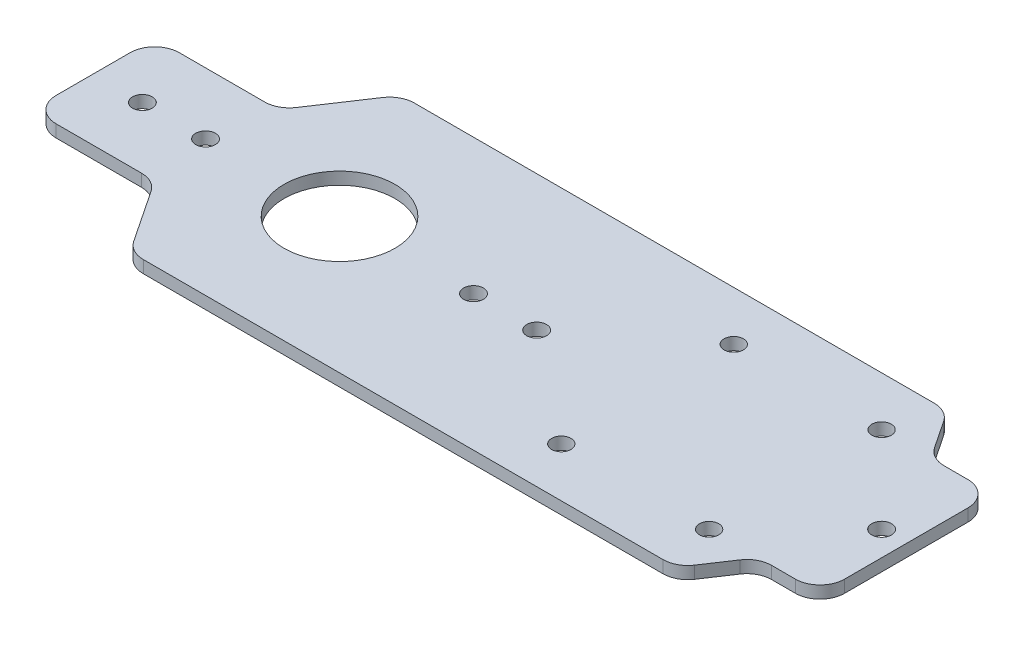
SolidWorks part; units mm, degrees
material "6061 Alloy"
ref_plane "Front Plane" through (0, 0, 0) normal (0, 0, 1) x (1, 0, 0)
ref_plane "Top Plane" through (0, 0, 0) normal (0, 1, 0) x (1, 0, 0)
ref_plane "Right Plane" through (0, 0, 0) normal (1, 0, 0) x (0, 0, -1)
sketch "Sketch1" plane through (0, 0, 0) normal (0, 1, 0) x (1, 0, 0)
  line L0 (16.2686, 0) -> (85.3314, 0) construction
  line L1 (50.8, 0) -> (50.8, 3.1391) construction
  line L2 (19.05, 15.875) -> (31.75, 34.925)
  line L3 (-12.7, 15.875) -> (19.05, 15.875)
  line L4 (-12.7, 15.875) -> (-12.7, -15.875)
  line L5 (-12.7, -15.875) -> (19.05, -15.875)
  line L6 (114.3, 15.875) -> (114.3, -15.875)
  line L7 (-12.7, 15.875) -> (114.3, -15.875) construction
  line L8 (-12.7, -15.875) -> (114.3, 15.875) construction
  line L9 (31.75, 34.925) -> (69.85, 34.925)
  line L10 (69.85, 34.925) -> (82.55, 15.875)
  line L11 (50.8, 34.925) -> (50.8, 29.0511) construction
  line L12 (69.85, -34.925) -> (82.55, -15.875)
  line L13 (31.75, -34.925) -> (69.85, -34.925)
  line L14 (19.05, -15.875) -> (31.75, -34.925)
  line L15 (82.55, -15.875) -> (114.3, -15.875)
  line L16 (82.55, 15.875) -> (114.3, 15.875)
  circle A0 centre (0, 0) radius 2.54
  circle A1 centre (101.6, 0) radius 2.54
  circle A2 centre (16.2686, 0) radius 2.54 construction
  circle A3 centre (85.3314, 0) radius 2.54 construction
  dimension "D1" = 5.08
  dimension "D3" = 127
  dimension "D4" = 31.75
  dimension "D5" = 69.0628
  dimension "D2" = 101.6
  dimension "D6" = 19.05
  dimension "D7" = 31.75
  dimension "D8" = 38.1
extrude "Boss-Extrude1" add sketch "Sketch1" along normal blind 3.175
sketch "Sketch2" plane through (0, 3.175, 0) normal (0, 1, 0) x (1, 0, 0)
  circle A0 centre (50.8, 0) radius 14.2875
  circle A1 centre (0, 0) radius 2.54 construction
  dimension "D1" = 50.8
  dimension "D2" = 28.575
extrude "Cut-Extrude1" cut sketch "Sketch2" against normal blind 3.175
sketch "Sketch3" plane through (0, 3.175, 0) normal (0, 1, 0) x (1, 0, 0)
  line L0 (50.8, 0) -> (50.8, 14.2875) construction
  circle A2 centre (85.3314, 0) radius 2.54
  circle A3 centre (16.2686, 0) radius 2.54
  circle A5 centre (50.8, 0) radius 14.2875 construction
  circle A6 centre (50.8, 0) radius 14.2875 construction
  dimension "D2" = 5.08
  dimension "D3" = 5.08
  dimension "D4" = 69.0628
extrude "Cut-Extrude2" cut sketch "Sketch3" against normal through all
sketch "Sketch5" plane through (0, 0, 0) normal (0, -1, 0) x (1, 0, 0)
  line L5 (114.3, 15.875) -> (114.3, -15.875) construction
  line L10 (69.85, -34.925) -> (196.85, -34.925)
  line L11 (69.85, -34.925) -> (69.85, 34.925)
  line L12 (69.85, 34.925) -> (196.85, 34.925)
  line L13 (196.85, -34.925) -> (196.85, 34.925)
  line L14 (114.554, 17.272) -> (183.896, 17.272) construction
  line L15 (114.554, 17.272) -> (114.554, -17.272) construction
  line L16 (114.554, -17.272) -> (183.896, -17.272) construction
  line L17 (183.896, 17.272) -> (183.896, -17.272) construction
  line L18 (172.5083, 34.925) -> (180.975, 22.225)
  line L19 (172.5083, -34.925) -> (180.975, -22.225)
  line L20 (180.975, -22.225) -> (196.85, -22.225)
  line L21 (82.55, -15.875) -> (69.85, -34.925) construction
  line L22 (82.55, -15.875) -> (69.85, -34.925)
  line L23 (69.85, 34.925) -> (82.55, 15.875) construction
  line L24 (69.85, 34.925) -> (82.55, 15.875)
  line L25 (180.975, 22.225) -> (196.85, 22.225)
  circle A4 centre (101.6, 0) radius 2.54 construction
  circle A5 centre (85.3314, 0) radius 2.54 construction
  circle A6 centre (101.6, 0) radius 2.54
  circle A7 centre (85.3314, 0) radius 2.54
  circle A8 centre (130.175, 22.225) radius 2.4892
  circle A9 centre (168.275, 22.225) radius 2.4892
  circle A10 centre (130.175, -22.225) radius 2.4892
  circle A11 centre (168.275, -22.225) radius 2.4892
  circle A12 centre (190.5, 0) radius 2.54
  line M15 (69.85, -34.925) -> (82.55, -15.875)
  line M16 (82.55, -15.875) -> (114.3, -15.875)
  line M17 (114.3, -15.875) -> (114.3, 15.875)
  line M18 (114.3, 15.875) -> (82.55, 15.875)
  line M19 (82.55, 15.875) -> (69.85, 34.925)
  dimension "D2" = 4.9784
  dimension "D3" = 44.45
  dimension "D4" = 38.1
  dimension "D11" = 15.621
  dimension "D16" = 88.9
  dimension "D5" = 4.953
  dimension "D6" = 82.55
  dimension "D7" = 17.653
  dimension "D8" = 0.254
  dimension "D9" = 69.342
  dimension "D10" = 34.544
  dimension "D12" = 15.875
  dimension "D13" = 12.7
  dimension "D14" = 15.875
  dimension "D15" = 12.7
extrude "Boss-Extrude2" add sketch "Sketch5" against normal up to surface (3.175 mm away) contours L25 L18 L12 L10 L19 L20 L13 A11 A10 A9 A8 M19 M18 M17 M16 M15 region at (139.8524, 0, 0) up to face at (85.3314, 3.175, 2.54)
fillet "Fillet1" radius 6.35 12 edges at (19.05, 1.5875, -15.875) (31.75, 1.5875, -34.925) (31.75, 1.5875, 34.925) (19.05, 1.5875, 15.875) (-12.7, 1.5875, -15.875) (-12.7, 1.5875, 15.875) (172.5083, 1.5875, -34.925) (180.975, 1.5875, -22.225) (196.85, 1.5875, -22.225) (196.85, 1.5875, 22.225) (180.975, 1.5875, 22.225) (172.5083, 1.5875, 34.925)
sketch "Sketch4"
sketch "Sketch6" plane through (0, 3.175, 0) normal (0, 1, 0) x (1, 0, 0)
  line L12 (179.0899, 25.0527) -> (174.3934, 32.0973)
  line L13 (169.1099, 34.925) -> (35.1484, 34.925)
  line L14 (29.8649, 32.0973) -> (20.9351, 18.7027)
  line L15 (15.6516, 15.875) -> (-6.35, 15.875)
  line L16 (-12.7, 9.525) -> (-12.7, -9.525)
  line L17 (-6.35, -15.875) -> (15.6516, -15.875)
  line L18 (20.9351, -18.7027) -> (29.8649, -32.0973)
  line L19 (35.1484, -34.925) -> (169.1099, -34.925)
  line L20 (174.3934, -32.0973) -> (179.0899, -25.0527)
  line L21 (184.3734, -22.225) -> (190.5, -22.225)
  line L22 (196.85, -15.875) -> (196.85, 15.875)
  line L23 (190.5, 22.225) -> (184.3734, 22.225)
  line L24 (179.0899, 25.0527) -> (174.3934, 32.0973)
  line L25 (169.1099, 34.925) -> (35.1484, 34.925)
  line L26 (29.8649, 32.0973) -> (20.9351, 18.7027)
  line L27 (15.6516, 15.875) -> (-6.35, 15.875)
  line L28 (-12.7, 9.525) -> (-12.7, -9.525)
  line L29 (-6.35, -15.875) -> (15.6516, -15.875)
  line L30 (20.9351, -18.7027) -> (29.8649, -32.0973)
  line L31 (35.1484, -34.925) -> (169.1099, -34.925)
  line L32 (174.3934, -32.0973) -> (179.0899, -25.0527)
  line L33 (184.3734, -22.225) -> (190.5, -22.225)
  line L34 (196.85, -15.875) -> (196.85, 15.875)
  line L35 (190.5, 22.225) -> (184.3734, 22.225)
  circle A0 centre (0, 0) radius 2.54 construction
  circle A1 centre (16.2686, 0) radius 2.54 construction
  circle A2 centre (50.8, 0) radius 14.2875 construction
  circle A3 centre (85.3314, 0) radius 2.54 construction
  circle A4 centre (130.175, -22.225) radius 2.4892 construction
  circle A5 centre (101.6, 0) radius 2.54 construction
  circle A6 centre (130.175, 22.225) radius 2.4892 construction
  circle A7 centre (168.275, 22.225) radius 2.4892 construction
  circle A8 centre (190.5, 0) radius 2.54 construction
  circle A9 centre (168.275, -22.225) radius 2.4892 construction
  circle A10 centre (0, 0) radius 2.54
  circle A11 centre (16.2686, 0) radius 2.54
  arc A12 (174.3934, 32.0973) -> (169.1099, 34.925) centre (169.1099, 28.575) ccw
  arc A13 (35.1484, 34.925) -> (29.8649, 32.0973) centre (35.1484, 28.575) ccw
  arc A14 (15.6516, 15.875) -> (20.9351, 18.7027) centre (15.6516, 22.225) ccw
  arc A15 (-6.35, 15.875) -> (-12.7, 9.525) centre (-6.35, 9.525) ccw
  arc A16 (-12.7, -9.525) -> (-6.35, -15.875) centre (-6.35, -9.525) ccw
  arc A17 (20.9351, -18.7027) -> (15.6516, -15.875) centre (15.6516, -22.225) ccw
  arc A18 (29.8649, -32.0973) -> (35.1484, -34.925) centre (35.1484, -28.575) ccw
  arc A19 (169.1099, -34.925) -> (174.3934, -32.0973) centre (169.1099, -28.575) ccw
  arc A20 (184.3734, -22.225) -> (179.0899, -25.0527) centre (184.3734, -28.575) ccw
  arc A21 (190.5, -22.225) -> (196.85, -15.875) centre (190.5, -15.875) ccw
  arc A22 (196.85, 15.875) -> (190.5, 22.225) centre (190.5, 15.875) ccw
  arc A23 (179.0899, 25.0527) -> (184.3734, 22.225) centre (184.3734, 28.575) ccw
  arc A24 (174.3934, 32.0973) -> (169.1099, 34.925) centre (169.1099, 28.575) ccw
  arc A25 (35.1484, 34.925) -> (29.8649, 32.0973) centre (35.1484, 28.575) ccw
  arc A26 (15.6516, 15.875) -> (20.9351, 18.7027) centre (15.6516, 22.225) ccw
  arc A27 (-6.35, 15.875) -> (-12.7, 9.525) centre (-6.35, 9.525) ccw
  arc A28 (-12.7, -9.525) -> (-6.35, -15.875) centre (-6.35, -9.525) ccw
  arc A29 (20.9351, -18.7027) -> (15.6516, -15.875) centre (15.6516, -22.225) ccw
  arc A30 (29.8649, -32.0973) -> (35.1484, -34.925) centre (35.1484, -28.575) ccw
  arc A31 (169.1099, -34.925) -> (174.3934, -32.0973) centre (169.1099, -28.575) ccw
  arc A32 (184.3734, -22.225) -> (179.0899, -25.0527) centre (184.3734, -28.575) ccw
  arc A33 (190.5, -22.225) -> (196.85, -15.875) centre (190.5, -15.875) ccw
  arc A34 (196.85, 15.875) -> (190.5, 22.225) centre (190.5, 15.875) ccw
  arc A35 (179.0899, 25.0527) -> (184.3734, 22.225) centre (184.3734, 28.575) ccw
  circle A36 centre (50.8, 0) radius 14.2875
  circle A37 centre (85.3314, 0) radius 2.54
  circle A38 centre (130.175, -22.225) radius 2.4892
  circle A39 centre (101.6, 0) radius 2.54
  circle A40 centre (130.175, 22.225) radius 2.4892
  circle A41 centre (168.275, 22.225) radius 2.4892
  circle A42 centre (190.5, 0) radius 2.54
  circle A43 centre (168.275, -22.225) radius 2.4892
  dimension "D1" = 0
